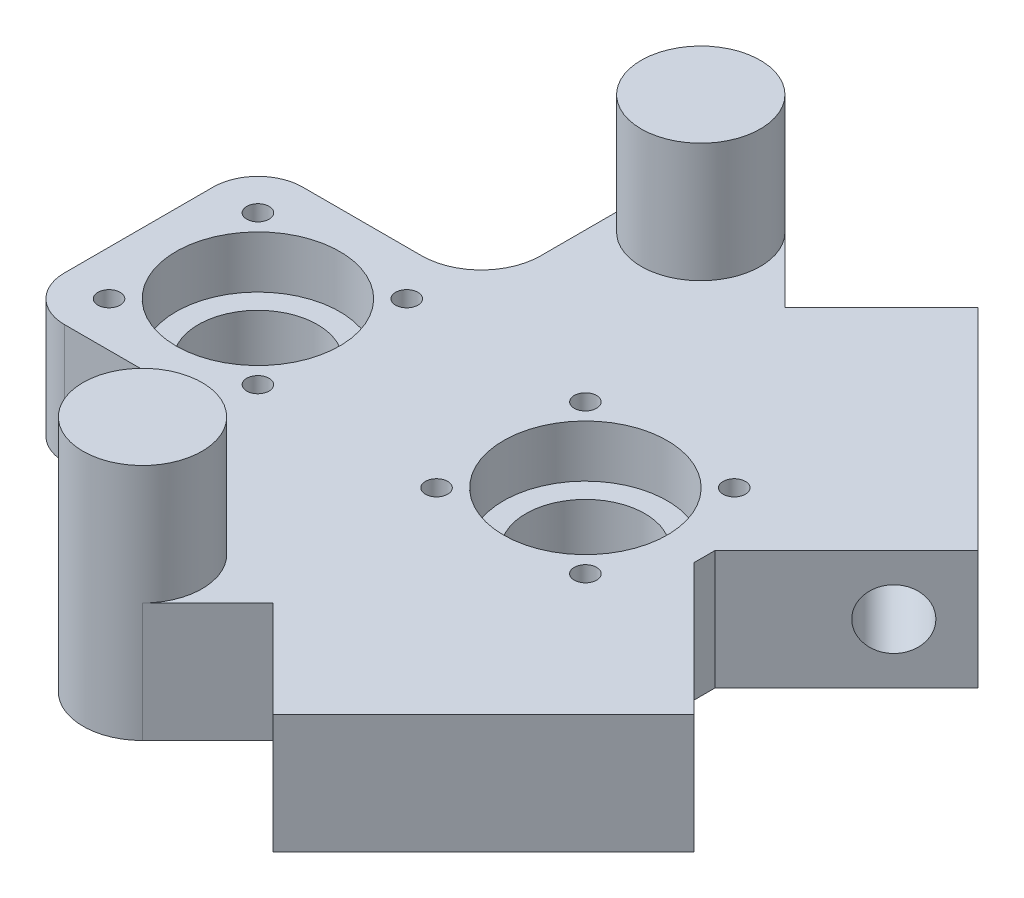
SolidWorks part; units mm, degrees
material "ABS"
ref_plane "Front Plane" through (0, 0, 0) normal (0, 0, 1) x (1, 0, 0)
ref_plane "Top Plane" through (0, 0, 0) normal (0, 1, 0) x (1, 0, 0)
ref_plane "Right Plane" through (0, 0, 0) normal (1, 0, 0) x (0, 0, -1)
sketch "Sketch1" plane through (0, 0, 0) normal (0, 1, 0) x (1, 0, 0)
  line L0 (-386.3027, 0) -> (412.614, 0) construction
  line L1 (0, -323.8826) -> (0, 265.8262) construction
  line L2 (0, 251.091) -> (251.091, 0)
  line L3 (160, 0) -> (80, 138.5641)
  line L4 (160, 0) -> (0, 0)
  line L5 (0, 239.7773) -> (239.7773, 0)
  line L6 (196.4046, 34.4091) -> (187.6569, 43.1569)
  line L7 (144, -10) -> (144, 10)
  line L8 (150, 16) -> (166, 16)
  line L9 (174, 24) -> (174, 37.5)
  line L11 (196.4046, 34.4091) -> (209.3717, 47.3762)
  line L12 (209.3717, 47.3762) -> (237.6559, 19.0919)
  line L13 (237.6559, 19.0919) -> (220, 1.4359)
  line L14 (220, 1.4359) -> (220, -1.4359)
  line L15 (237.6559, -19.0919) -> (220, -1.4359)
  line L16 (209.3717, -47.3762) -> (237.6559, -19.0919)
  line L17 (196.4046, -34.4091) -> (209.3717, -47.3762)
  line L18 (187.6569, -43.1569) -> (196.4046, -34.4091)
  line L19 (174, -24) -> (174, -37.5)
  line L20 (150, -16) -> (166, -16)
  circle A0 centre (0, 0) radius 160
  circle A1 centre (160, 0) radius 11
  circle A2 centre (150, 10) radius 1.5
  circle A3 centre (170, 10) radius 1.5
  circle A4 centre (170, -10) radius 1.5
  circle A5 centre (150, -10) radius 1.5
  circle A6 centre (204, 0) radius 11
  circle A7 centre (182, 37.5) radius 4
  circle A8 centre (80, 138.5641) radius 15
  circle A9 centre (194, 10) radius 1.5
  circle A10 centre (214, 10) radius 1.5
  circle A11 centre (214, -10) radius 1.5
  circle A12 centre (194, -10) radius 1.5
  arc A13 (144, 10) -> (150, 16) centre (150, 10) cw
  arc A14 (174, 37.5) -> (187.6569, 43.1569) centre (182, 37.5) cw
  arc A15 (166, 16) -> (174, 24) centre (166, 24) ccw
  circle A16 centre (182, -37.5) radius 4
  arc A17 (174, -37.5) -> (187.6569, -43.1569) centre (182, -37.5) ccw
  arc A18 (166, -16) -> (174, -24) centre (166, -24) cw
  arc A19 (144, -10) -> (150, -16) centre (150, -10) ccw
  circle A20 centre (160, 0) radius 8
  circle A21 centre (204, 0) radius 8
  point P53 (220, 0)
  point P65 (144, 0)
  dimension "D1" = 320
  dimension "D2" = 22
  dimension "D5" = 3
  dimension "D10" = 22
  dimension "D13" = 30
  dimension "D11" = 8
  dimension "D14" = 8
  dimension "D18" = 3
  dimension "D25" = 6
  dimension "D28" = 8
  dimension "D33" = 16
  dimension "D34" = 16
  dimension "D15" = 8
  dimension "D3" = 10
  dimension "D4" = 10
  dimension "D8" = 45
  dimension "D9" = 160
  dimension "D12" = 37.5
  dimension "D16" = 44
  dimension "D17" = 22
  dimension "D19" = 10
  dimension "D20" = 10
  dimension "D23" = 16
  dimension "D24" = 16
  dimension "D26" = 8
  dimension "D27" = 15
  dimension "D29" = 4
  dimension "D31" = 16
  dimension "D32" = 40
  dimension "D6" = 2
  dimension "D7" = 2
  dimension "D21" = 2
  dimension "D22" = 2
extrude "Boss-Extrude1" add sketch "Sketch1" along normal blind 16 contours L20 A18 L19 A17 L18 L17 L16 L15 L14 L13 L5 L11 L9 A15 L8 A0 A1 A16 A12 A11 A10 A9 A7 A6 A4 A3 | A13 L7 L4 A1 L3 L8 A2 | A1 A0 L8 L3 | L7 A19 L20 A0 A1 L4 A5 | L13 L2 L11 L5 | L13 L12 L11 L2 | A7 | A16 region at (222.0996, 0, -31.8198) region at (217.857, 0, -27.5772) region at (214.1688, 0, -23.889) region at (154.599, 0, 15.7764) region at (155.7484, 0, -13.3869) region at (147.953, 0, -8.215) region at (182, 0, -37.5) region at (182, 0, 37.5)
extrude "Boss-Extrude2" add sketch "Sketch1<4>" along normal blind 9 contours A6 A21 region at (193.3111, 0, 0)
sketch "Sketch1<4>" plane through (0, 0, 0) normal (0, 1, 0) x (1, 0, 0) same geometry as "Sketch1"
sketch "Sketch2" plane through (109.282, 0, 109.282) normal (0.7071, 0, 0.7071) x (0.7071, 0, -0.7071)
  line L0 (181.5481, 16) -> (156.5789, 16) construction
  line L1 (181.5481, 16) -> (181.5481, 0) construction
  circle A0 centre (173.5481, 8) radius 4
  dimension "D1" = 8
  dimension "D2" = 8
  dimension "D3" = 8
extrude "Cut-Extrude1" cut sketch "Sketch2" against normal through all
sketch "Sketch3" plane through (109.282, 0, -109.282) normal (0.7071, 0, -0.7071) x (-0.7071, 0, -0.7071)
  line L0 (-181.5481, 16) -> (-181.5481, 0) construction
  line L1 (-181.5481, 0) -> (-156.5789, 0) construction
  circle A0 centre (-173.5481, 8) radius 4
  dimension "D1" = 8
  dimension "D2" = 8
  dimension "D3" = 8
extrude "Cut-Extrude2" cut sketch "Sketch3" against normal through all
ref_point "Point1"
extrude "Boss-Extrude3" add sketch "Sketch1<5>" along normal blind 9 contours A20 A0 A1 | A20 L4 A1 A0 | A20 L3 A1 L4 | A20 A0 A1 L3 region at (153.7862, 0, 6.029) region at (159.9652, 0, 9.5106) region at (157.4093, 0, -9.1164) region at (152.0783, 0, -4.5736)
sketch "Sketch1<5>" plane through (0, 0, 0) normal (0, 1, 0) x (1, 0, 0) same geometry as "Sketch1"
sketch "Sketch4" plane through (0, 0, 0) normal (0, -1, 0) x (1, 0, 0)
  line L1 (153.4641, 10) -> (151.7321, 13)
  line L2 (151.7321, 13) -> (148.2679, 13)
  line L3 (148.2679, 13) -> (146.5359, 10)
  line L4 (146.5359, 10) -> (148.2679, 7)
  line L5 (148.2679, 7) -> (151.7321, 7)
  line L6 (151.7321, 7) -> (153.4641, 10)
  line L7 (173.4641, 10) -> (171.7321, 13)
  line L8 (171.7321, 13) -> (168.2679, 13)
  line L9 (168.2679, 13) -> (166.5359, 10)
  line L10 (166.5359, 10) -> (168.2679, 7)
  line L11 (168.2679, 7) -> (171.7321, 7)
  line L12 (171.7321, 7) -> (173.4641, 10)
  line L13 (153.4641, -10) -> (151.7321, -7)
  line L14 (151.7321, -7) -> (148.2679, -7)
  line L15 (148.2679, -7) -> (146.5359, -10)
  line L16 (146.5359, -10) -> (148.2679, -13)
  line L17 (148.2679, -13) -> (151.7321, -13)
  line L18 (151.7321, -13) -> (153.4641, -10)
  line L19 (173.4641, -10) -> (171.7321, -7)
  line L20 (171.7321, -7) -> (168.2679, -7)
  line L21 (168.2679, -7) -> (166.5359, -10)
  line L22 (166.5359, -10) -> (168.2679, -13)
  line L23 (168.2679, -13) -> (171.7321, -13)
  line L24 (171.7321, -13) -> (173.4641, -10)
  line L25 (197.4641, 10) -> (195.7321, 13)
  line L26 (195.7321, 13) -> (192.2679, 13)
  line L27 (192.2679, 13) -> (190.5359, 10)
  line L28 (190.5359, 10) -> (192.2679, 7)
  line L29 (192.2679, 7) -> (195.7321, 7)
  line L30 (195.7321, 7) -> (197.4641, 10)
  line L31 (217.4641, 10) -> (215.7321, 13)
  line L32 (215.7321, 13) -> (212.2679, 13)
  line L33 (212.2679, 13) -> (210.5359, 10)
  line L34 (210.5359, 10) -> (212.2679, 7)
  line L35 (212.2679, 7) -> (215.7321, 7)
  line L36 (215.7321, 7) -> (217.4641, 10)
  line L37 (197.4641, -10) -> (195.7321, -7)
  line L38 (195.7321, -7) -> (192.2679, -7)
  line L39 (192.2679, -7) -> (190.5359, -10)
  line L40 (190.5359, -10) -> (192.2679, -13)
  line L41 (192.2679, -13) -> (195.7321, -13)
  line L42 (195.7321, -13) -> (197.4641, -10)
  line L43 (217.4641, -10) -> (215.7321, -7)
  line L44 (215.7321, -7) -> (212.2679, -7)
  line L45 (212.2679, -7) -> (210.5359, -10)
  line L46 (210.5359, -10) -> (212.2679, -13)
  line L47 (212.2679, -13) -> (215.7321, -13)
  line L48 (215.7321, -13) -> (217.4641, -10)
  circle A0 centre (150, 10) radius 3 construction
  circle A1 centre (170, 10) radius 3 construction
  circle A2 centre (150, -10) radius 3 construction
  circle A3 centre (170, -10) radius 3 construction
  circle A4 centre (194, 10) radius 3 construction
  circle A5 centre (214, 10) radius 3 construction
  circle A6 centre (194, -10) radius 3 construction
  circle A7 centre (214, -10) radius 3 construction
extrude "Cut-Extrude3" cut sketch "Sketch4" against normal blind 2.5
sketch "Sketch5" plane through (0, 16, 0) normal (0, 1, 0) x (1, 0, 0)
  circle A0 centre (182, -37.5) radius 8
  circle A1 centre (182, 37.5) radius 8
  arc A2 (174, -37.5) -> (187.6569, -43.1569) centre (182, -37.5) ccw construction
  arc A3 (187.6569, 43.1569) -> (174, 37.5) centre (182, 37.5) ccw construction
extrude "Boss-Extrude4" add sketch "Sketch5" along normal blind 32 from surface starting at face at (214, 0, -10)
extrude "Cut-Extrude4" cut sketch "Sketch1<6>" along normal blind 28 contours A16 | A7 region at (182, 0, -37.5) region at (182, 0, 37.5)
sketch "Sketch1<6>" plane through (0, 0, 0) normal (0, 1, 0) x (1, 0, 0) same geometry as "Sketch1"
equation "\"rod_diameter\"= 8"
equation "\"rod_hole_thickness\"= 4"
equation "\"rod_radius\"= \"rod_diameter\" / 2"
equation "\"platter_diameter\"= 320"
equation "\"platter_radius\"= \"platter_diameter\" / 2"
equation "\"extruder_mount_hole_spacing\"= 50"
equation "\"arm_rod_spacing\"= 40"
equation "\"D1@Sketch1\"=\"platter_diameter\""
equation "\"D9@Sketch1\"=\"platter_radius\""
equation "\"D11@Sketch1\"=\"rod_diameter\""
equation "\"D14@Sketch1\"=\"rod_diameter\""
equation "\"D12@Sketch1\"=\"z_rod_spacing\"/2"
equation "\"D26@Sketch1\"=\"rod_radius\"+\"rod_hole_thickness\""
equation "\"D28@Sketch1\"=\"rod_radius\"+\"rod_hole_thickness\""
equation "\"D29@Sketch1\"=\"rod_hole_thickness\""
equation "\"D1@Boss-Extrude2\"= \"D1@Boss-Extrude1\" - 7"
equation "\"D1@Sketch2\" = \"rod_diameter\""
equation "\"D2@Sketch2\"= \"D1@Boss-Extrude1\" / 2"
equation "\"D3@Sketch2\"=\"rod_radius\"+\"rod_hole_thickness\""
equation "\"D1@Sketch3\"=\"rod_diameter\""
equation "\"D2@Sketch3\"=\"rod_radius\"+\"rod_hole_thickness\""
equation "\"D3@Sketch3\"= \"D1@Boss-Extrude1\" / 2"
equation "\"D1@Boss-Extrude1\" = \"rod_diameter\" + \"rod_hole_thickness\" * 2"
equation "\"D1@Boss-Extrude3\"= \"D1@Boss-Extrude1\" - 7"
equation "\"top_frame_rod_spacing\"= \"arm_rod_spacing\" + 40"
equation "\"motor_level_rod_spacing\"= 15"
equation "\"linear_bearing_diameter\"= 15"
equation "\"platter_rod_spacing\"= 50"
equation "\"z_rod_spacing\"= 75"
equation "\"D15@Sketch1\"=\"rod_radius\"+\"rod_hole_thickness\""
